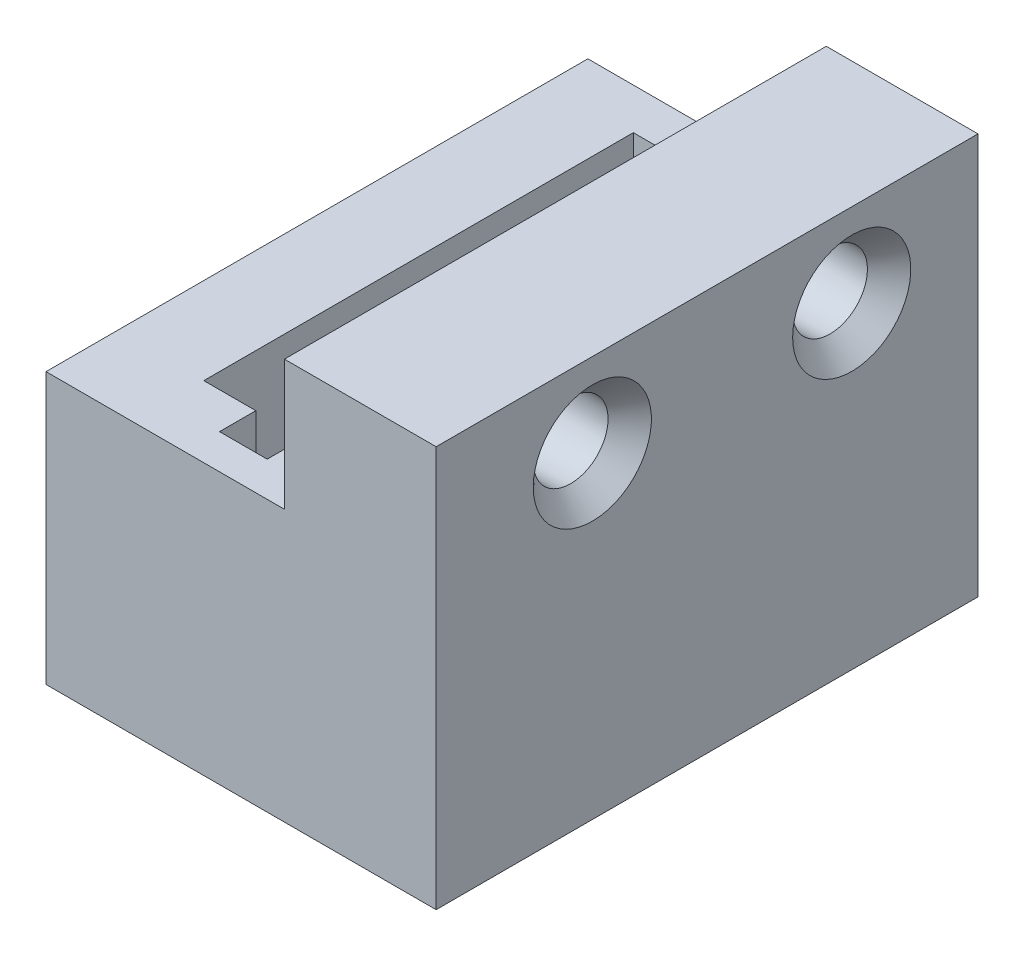
SolidWorks part; units mm, degrees
ref_plane "Front Plane" through (0, 0, 0) normal (0, 0, 1) x (1, 0, 0)
ref_plane "Top Plane" through (0, 0, 0) normal (0, 1, 0) x (1, 0, 0)
ref_plane "Right Plane" through (0, 0, 0) normal (1, 0, 0) x (0, 0, -1)
sketch "Sketch1" plane through (0, 0, 0) normal (0, 1, 0) x (1, 0, 0)
  line L1 (0, 0) -> (18, 0)
  line L2 (0, 0) -> (0, 25)
  line L3 (0, 25) -> (18, 25)
  line L4 (18, 0) -> (18, 25)
  dimension "D1" = 25
  dimension "D2" = 18
extrude "Boss-Extrude1" add sketch "Sketch1" along normal blind 12.5
sketch "Sketch2" plane through (0, 12.5, 0) normal (0, 1, 0) x (1, 0, 0)
  line L0 (18, 0) -> (18, 25) construction
  line L1 (4, 23.0983) -> (6.4, 23.0983)
  line L2 (4, 23.0983) -> (4, 3.2803)
  line L3 (4, 3.2803) -> (6.4, 3.2803)
  line L4 (11, 23.0983) -> (11, 3.2803)
  line L5 (7.5, 25) -> (7.5, 1.6053) construction
  line L6 (6.4, 23.0983) -> (6.4, 25)
  line L7 (18, 25) -> (0, 25) construction
  line L8 (6.4, 25) -> (8.6, 25)
  line L9 (8.6, 25) -> (8.6, 23.0983)
  line L10 (8.6, 23.0983) -> (11, 23.0983)
  line L11 (6.4, 3.2803) -> (6.4, 1.6053)
  line L12 (6.4, 1.6053) -> (8.6, 1.6053)
  line L13 (8.6, 1.6053) -> (8.6, 3.2803)
  line L14 (8.6, 3.2803) -> (11, 3.2803)
  dimension "D1" = 19.818
  dimension "D2" = 7
  dimension "D3" = 7
  dimension "D4" = 2.2
  dimension "D5" = 1.675
extrude "Cut-Extrude1" cut sketch "Sketch2" against normal blind 6.056
ref_plane "PLANE-CAVITY-MIDLINE" through (7.5, 0, 0) normal (1, 0, 0) x (0, 0, -1)
sketch "Sketch4" plane through (0, 12.5, 0) normal (0, 1, 0) x (1, 0, 0)
  line L0 (0, 0) -> (18, 0) construction
  line L1 (11, 0) -> (18, 0)
  line L2 (11, 0) -> (11, 25)
  line L3 (11, 25) -> (18, 25)
  line L4 (18, 0) -> (18, 25)
  line L5 (11, 3.2803) -> (11, 23.0983) construction
extrude "Boss-Extrude2" add sketch "Sketch4" along normal blind 6
sketch "Sketch3" plane through (18, 0, 0) normal (1, 0, 0) x (0, 0, -1)
  line L0 (3.2803, 6.444) -> (23.0983, 6.444) construction
  line L3 (3.2803, 6.444) -> (23.0983, 6.444) construction
  line L8 (13.1893, 6.444) -> (13.1893, -49993.556) construction
  circle A0 centre (7.2053, 14.644) radius 1.725
  circle A1 centre (19.1733, 14.644) radius 1.725
  circle A2 centre (7.2053, 14.644) radius 1.25 construction
  point P7 (13.1893, 6.444)
  dimension "D1" = 3.45
  dimension "D2" = 10.243
extrude "Cut-Extrude2" cut sketch "Sketch3" against normal up to surface (7 mm away) up to face at (11, 12.486, -12.8446)
sketch "Sketch6" plane through (0, 6.444, 0) normal (0, 1, 0) x (1, 0, 0)
  line L0 (5.875, 9.6053) -> (5.875, 3.2803) construction
  line L1 (4, 3.2803) -> (6.4, 3.2803) construction
  line L2 (9.125, 3.2803) -> (9.125, 9.6053) construction
  line L3 (8.6, 3.2803) -> (11, 3.2803) construction
  line L4 (9.125, 9.6053) -> (9.125, 17.6053) construction
  line L5 (9.125, 17.6053) -> (5.875, 17.6053) construction
  line L6 (5.875, 17.6053) -> (5.875, 9.6053) construction
  line L7 (5.875, 9.6053) -> (7.5, 9.6053) construction
  line L8 (7.5, -6.6308) -> (7.5, 6.6308) construction
  line L9 (7.5, 9.6053) -> (9.125, 9.6053) construction
  circle A0 centre (5.875, 9.6053) radius 0.5
  circle A1 centre (9.125, 9.6053) radius 0.5
  circle A2 centre (5.875, 17.6053) radius 0.5
  circle A3 centre (9.125, 17.6053) radius 0.5
  dimension "D1" = 1
  dimension "D2" = 8
  dimension "D3" = 1.625
  dimension "D4" = 6.325
extrude "Cut-Extrude3" cut sketch "Sketch6" against normal blind 4
sketch "Sketch7" plane through (0, 6.444, 0) normal (0, 1, 0) x (1, 0, 0)
  line L0 (7.5, 1.6053) -> (7.5, 5.6053) construction
  line L1 (6.4, 1.6053) -> (8.6, 1.6053) construction
  line L2 (7.5, -6.6308) -> (7.5, 6.6308) construction
  line L3 (7.5, 5.6053) -> (7.5, 13.6053) construction
  line L4 (7.5, 13.6053) -> (7.5, 21.6053) construction
  line L5 (8.6, 3.2803) -> (11, 3.2803) construction
  circle A0 centre (7.5, 21.6053) radius 1.5
  circle A1 centre (7.5, 13.6053) radius 1.5
  circle A2 centre (7.5, 5.6053) radius 1.5
  dimension "D2" = 8
  dimension "D3" = 8
  dimension "D1" = 2.325
  dimension "D4" = 3
extrude "Cut-Extrude4" cut sketch "Sketch7" against normal blind 2
chamfer "Chamfer1" distance 1 angle 45 2 edges at (18, 14.644, -20.8983) (18, 14.644, -8.9303)
